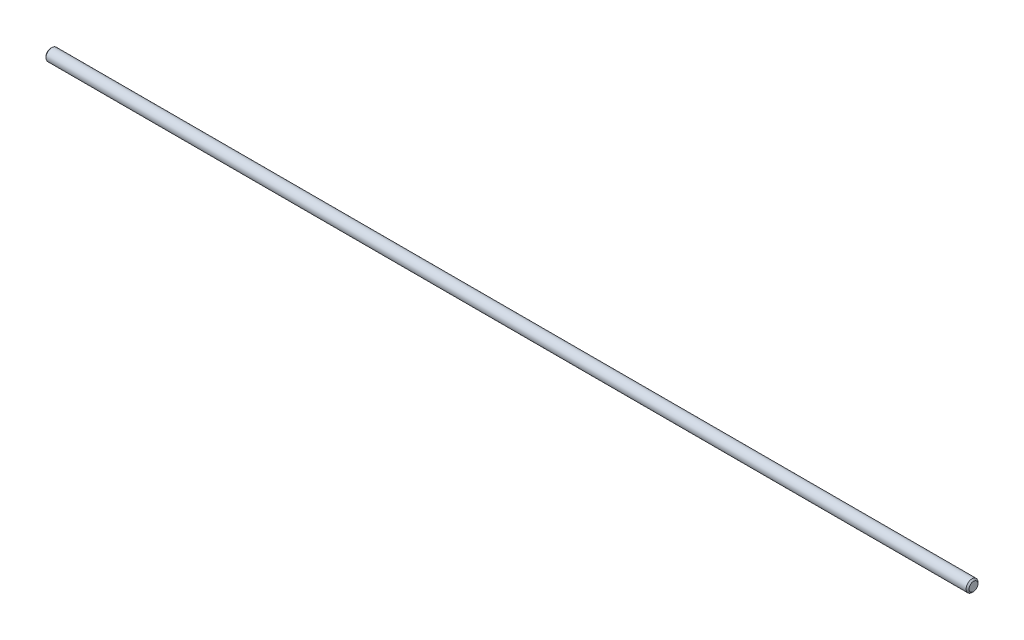
SolidWorks part; units mm, degrees
ref_plane "Front Plane" through (0, 0, 0) normal (0, 0, 1) x (1, 0, 0)
ref_plane "Top Plane" through (0, 0, 0) normal (0, 1, 0) x (1, 0, 0)
ref_plane "Right Plane" through (0, 0, 0) normal (1, 0, 0) x (0, 0, -1)
sketch "Sketch1" plane through (0, 0, 0) normal (0, 0, 1) x (1, 0, 0)
  line L0 (-77.5, 0) -> (77.5, 0) construction
  line L1 (77.5, 1) -> (77.5, -1) construction
  line L2 (-77.5, 1) -> (-77.5, -1) construction
  point P6 (76.1, -1)
  dimension "D1" = 1.4
  dimension "Thread Diameter" = 2
  dimension "Length" = 155
sketch "Sketch2" plane through (0, 0, 0) normal (1, 0, 0) x (0, 0, -1)
  circle A0 centre (0, 0) radius 1
extrude "Boss-Extrude1" add sketch "Sketch2" against normal up to vertex (77.5 mm away) and the other way up to vertex (77.5 mm away) up to point (-77.5, 0, 0) other way up to point (77.5, 0, 0)
sketch "Sketch3" plane through (77.5, 0, 0) normal (1, 0, 0) x (0, 0, -1)
  circle A1 centre (0, 0) radius 1
  circle A2 centre (0, 0) radius 1
  dimension "D1" = 0
curve "Helix/Spiral1" pitch 0.4 height 101 turns 252.5
sketch "Sketch4" plane through (0, 0, 0) normal (0, 0, 1) x (1, 0, 0)
  line L1 (77.4714, 1.0495) -> (77.8714, 1.0495) construction
  line L2 (77.4714, 1.0495) -> (77.6714, 0.7031) construction
  line L3 (77.6714, 0.7031) -> (77.8714, 1.0495) construction
  line L4 (77.6714, 1.0495) -> (77.6714, 1) construction
  line L5 (77.6714, 0.7031) -> (77.6714, 0.7526) construction
  line L6 (77.6429, 0.7526) -> (77.7, 0.7526) construction
  line L7 (77.5, 1) -> (77.8429, 1) construction
  line L8 (77.5, 1) -> (77.6429, 0.7526)
  line L9 (77.6429, 0.7526) -> (77.7, 0.7526)
  line L10 (77.7, 0.7526) -> (77.8429, 1)
  line L11 (77.8429, 1) -> (77.5, 1)
  dimension "Pitch" = 0.4
  dimension "D2" = 0.0571
sketch "Sketch5" plane through (77.5, 0, 0) normal (1, 0, 0) x (0, 0, -1)
  circle A0 centre (0, 0) radius 0.7526
extrude "Cut-Extrude1" cut sketch "Sketch5" against normal through all draft 45 flip side to cut
mirror "Mirror1" about plane through (0, 0, 0) normal (1, 0, 0) of "Cut-Extrude1"
equation "\"D2@Sketch4\" = \"Pitch@Sketch4\"/7"
